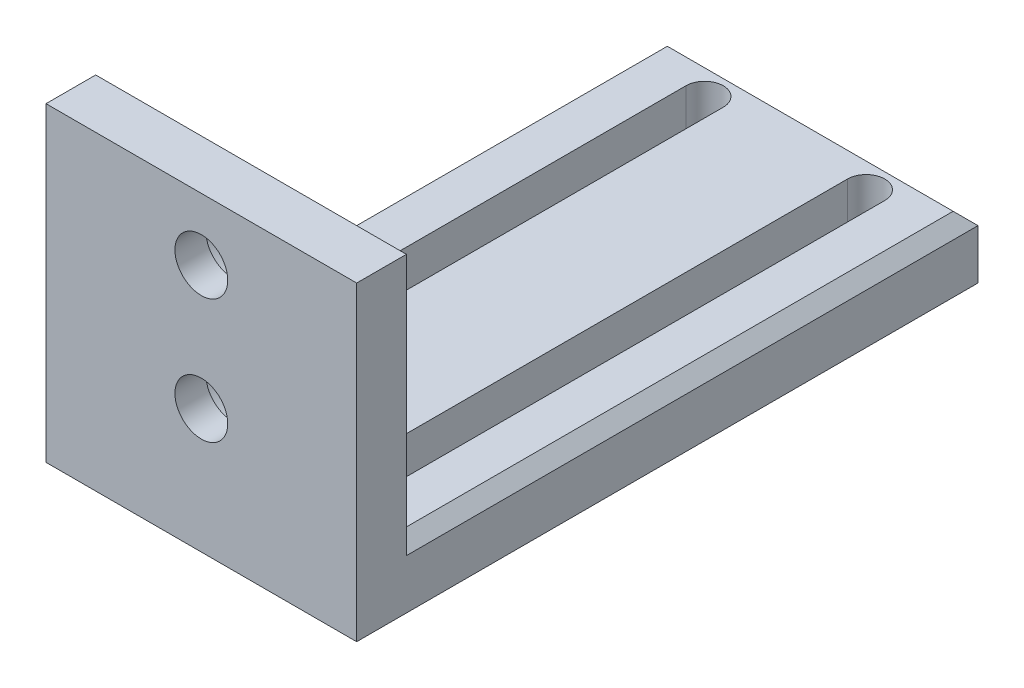
SolidWorks part; units mm, degrees
ref_plane "Płaszczyzna przednia" through (0, 0, 0) normal (0, 0, 1) x (1, 0, 0)
ref_plane "Płaszczyzna górna" through (0, 0, 0) normal (0, 1, 0) x (1, 0, 0)
ref_plane "Płaszczyzna prawa" through (0, 0, 0) normal (1, 0, 0) x (0, 0, -1)
sketch "Sketch1" plane through (0, 0, 0) normal (0, 1, 0) x (1, 0, 0)
  line L0 (0, 45) -> (50, 45) construction
  line L1 (0, 0) -> (50, 0)
  line L2 (0, 0) -> (0, 90)
  line L3 (0, 90) -> (50, 90)
  line L4 (50, 0) -> (50, 90)
  line L5 (12, 6) -> (12, 84) construction
  line L6 (9, 6) -> (9, 84)
  line L7 (15, 6) -> (15, 84)
  line L8 (38, 6) -> (38, 84) construction
  line L9 (35, 6) -> (35, 84)
  line L10 (41, 6) -> (41, 84)
  arc A0 (9, 6) -> (15, 6) centre (12, 6) ccw
  arc A1 (15, 84) -> (9, 84) centre (12, 84) ccw
  arc A2 (35, 6) -> (41, 6) centre (38, 6) ccw
  arc A3 (41, 84) -> (35, 84) centre (38, 84) ccw
  point P9 (12, 45)
  point P15 (38, 45)
  dimension "D1" = 50
  dimension "D2" = 90
  dimension "D3" = 6
  dimension "D4" = 6
  dimension "D5" = 12
  dimension "D6" = 12
extrude "Boss-Extrude1" add sketch "Sketch1" along normal blind 10
sketch "Sketch2" plane through (0, 0, 0) normal (0, 0, 1) x (1, 0, 0)
  line L0 (0, 10) -> (0, 0) construction
  line L1 (50, 0) -> (0, 0)
  line L2 (50, 0) -> (50, 50)
  line L3 (50, 50) -> (0, 50)
  line L4 (0, 0) -> (0, 50)
  line L5 (25, 50) -> (25, 0) construction
  circle A0 centre (25, 40) radius 4.25
  circle A1 centre (25, 20) radius 4.25
  dimension "D4" = 8.5
  dimension "D1" = 50
  dimension "D2" = 10
  dimension "D3" = 20
extrude "Boss-Extrude2" add sketch "Sketch2" along normal blind 10
sketch "Sketch3" plane through (0, 0, 0) normal (0, 0, -1) x (-1, 0, 0)
  circle A0 centre (-25, 40) radius 8.5
  circle A1 centre (-25, 20) radius 8.5
  dimension "D1" = 17
  dimension "D2" = 17
extrude "Cut-Extrude1" cut sketch "Sketch3" against normal blind 5
chamfer "Chamfer1" distance 2 angle 45 6 edges at (0, 30, 0) (25, 50, 0) (50, 30, 0) (50, 10, -45) (25, 10, -90) (0, 10, -45)
